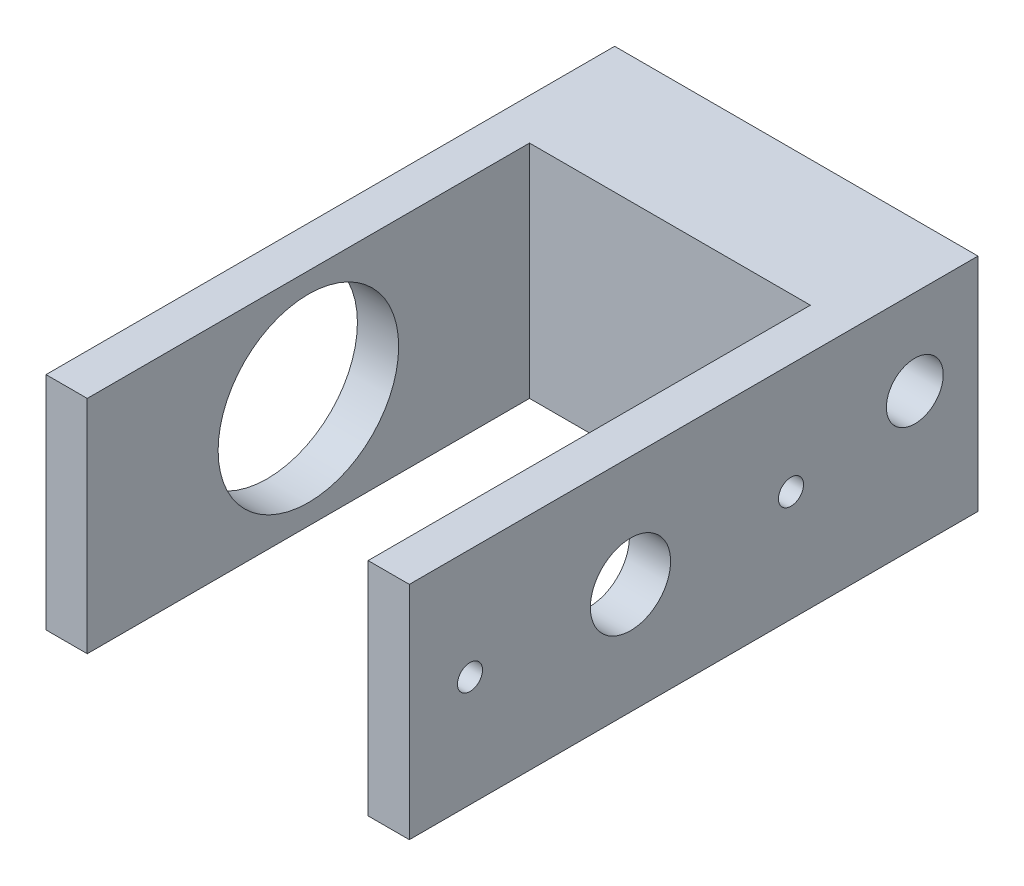
SolidWorks part; units mm, degrees
ref_plane "Front" through (0, 0, 0) normal (0, 0, 1) x (1, 0, 0)
ref_plane "Top" through (0, 0, 0) normal (0, 1, 0) x (1, 0, 0)
ref_plane "Right" through (0, 0, 0) normal (1, 0, 0) x (0, 0, -1)
sketch "Sketch1" plane through (0, 0, 0) normal (1, 0, 0) x (0, 0, -1)
  line L1 (-35, 17.5) -> (55, 17.5)
  line L2 (-35, 17.5) -> (-35, -17.5)
  line L3 (-35, -17.5) -> (55, -17.5)
  line L4 (55, 17.5) -> (55, -17.5)
  circle A0 centre (0, 0) radius 14.2875
  circle A1 centre (45, 4) radius 4.5
  point P9 (-35, 0)
  dimension "D2" = 45
  dimension "D1" = 4
  dimension "D3" = 0
  dimension "D4" = 35
  dimension "D5" = 90
  dimension "D6" = 10
extrude "Boss-Extrude1" add sketch "Sketch1" along normal blind 6.5278
sketch "Sketch2" plane through (6.5278, 0, 0) normal (1, 0, 0) x (0, 0, -1)
  line L0 (35, 17.5) -> (35, -17.5)
  line L1 (55, 17.5) -> (-35, 17.5) construction
  line L2 (-35, -17.5) -> (55, -17.5) construction
  circle A1 centre (45, 4) radius 4.5
  line M4 (-35, -17.5) -> (55, -17.5)
  line M5 (55, -17.5) -> (55, 17.5)
  line M6 (55, 17.5) -> (-35, 17.5)
  circle M7 centre (45, 4) radius 4.5
  dimension "D1" = 10
extrude "Boss-Extrude2" add sketch "Sketch2" along normal blind 44.45 contours L0 M6 M4 M5 M7 region at (6.5278, 17.0969, -45)
sketch "Sketch3" plane through (50.9778, 0, 0) normal (1, 0, 0) x (0, 0, -1)
  line L0 (-35, 0) -> (0, 0)
  line L1 (55, -17.5) -> (-35, -17.5)
  line L2 (55, -17.5) -> (55, 17.5)
  line L3 (55, 17.5) -> (-35, 17.5)
  line L4 (-35, -17.5) -> (-35, 17.5)
  line L5 (0, 0) -> (25.4, 0)
  line L6 (25.4, 0) -> (-25.4, 0)
  circle A0 centre (25.4, 0) radius 1.9844
  circle A1 centre (-25.4, 0) radius 1.9844
  circle A2 centre (0, 0) radius 6.35
  circle M2 centre (45, 4) radius 4.5
  line M4 (35, 17.5) -> (35, -17.5)
  line M5 (35, -17.5) -> (55, -17.5)
  line M6 (55, -17.5) -> (55, 17.5)
  dimension "D4" = 35
  dimension "D1" = 90
  dimension "D2" = 25.4
  dimension "D3" = 25.4
extrude "Boss-Extrude3" add sketch "Sketch3" along normal blind 6.5278 contours A1 A0 L4 L1 L3 M4 | L3 M6 M4 M5 M2 region at (50.9778, 8.75, 34.2174) region at (50.9778, 0, -35.4031)
